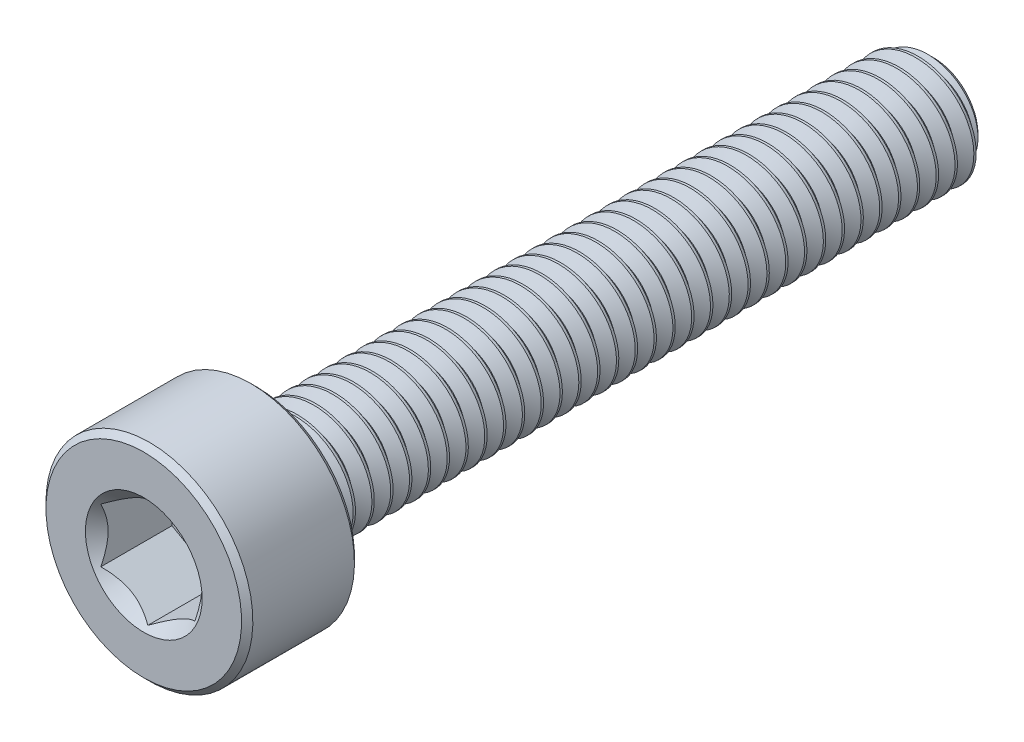
SolidWorks part; units mm, degrees
ref_plane "Front Plane" through (0, 0, 0) normal (0, 0, 1) x (1, 0, 0)
ref_plane "Top Plane" through (0, 0, 0) normal (0, 1, 0) x (1, 0, 0)
ref_plane "Right Plane" through (0, 0, 0) normal (1, 0, 0) x (0, 0, -1)
sketch "Sketch1" plane through (0, 0, 0) normal (1, 0, 0) x (0, 0, -1)
  line L0 (-10.5, 0) -> (10.5, 0) construction
  line L1 (10.5, 0) -> (10.5, 1.1752) construction
  line L2 (10.5, 1.1752) -> (10.1752, 1.5) construction
  line L3 (10.1752, 1.5) -> (10.125, 1.5) construction
  line L4 (10.125, 1.5) -> (-7.5, 1.5) construction
  line L5 (-7.5, 1.5) -> (-7.5, 2.75) construction
  line L6 (-7.5, 2.75) -> (-10.5, 2.75) construction
  line L7 (-10.5, 2.75) -> (-10.5, 0) construction
  line L8 (10.5, 1.1752) -> (10.5, 1.5) construction
  line L9 (10.4688, 1.5541) -> (10.7188, 1.1211) construction
  line L10 (10.7188, 1.1211) -> (10.9688, 1.5541) construction
  line L11 (10.9688, 1.5541) -> (10.4688, 1.5541) construction
  line L12 (10.7188, 1.5541) -> (10.7188, 1.5) construction
  line L13 (10.7188, 1.1211) -> (10.7188, 1.1752) construction
  line L14 (10.6875, 1.1752) -> (10.75, 1.1752) construction
  line L15 (10.5, 1.5) -> (10.9375, 1.5) construction
  line L16 (10.4844, 1.5271) -> (10.9531, 1.5271) construction
  line L17 (10.5, 0) -> (10.5, -1.5) construction
  line L18 (-7.65, 2.75) -> (-7.5, 2.6) construction
  line L19 (-10.35, 2.75) -> (-10.5, 2.6) construction
  line L20 (-7.5, 1.5) -> (-7.5, 0) construction
  line L21 (-7.5, 0.75) -> (-1.5, 0.75) construction
  line L22 (-1.5, 0.75) -> (4.5, 0.75) construction
  line L23 (4.5, 0.75) -> (10.5, 0.75) construction
  line L24 (-1.5, 0.75) -> (-1.5, 1.5) construction
  line L25 (-1.5, 1.5) -> (-1.5, 2.75) construction
  line L26 (4.5, 0.75) -> (4.5, 2.75) construction
  point P0 (-10.5, 1.25)
  point P3 (9.25, 1.5)
  point P4 (0, 0)
  point P18 (4.5, 1.5)
  point P22 (10.7188, 1.1752)
  point P24 (10.125, 1.5)
  point P25 (10.7188, 1.5)
  point P28 (10.7188, 1.5271)
  point P29 (9.25, -1.5)
  point P30 (-1.5, 1.5)
  point P31 (-9, 2.75)
  point P37 (-8.025, 2.75)
  point P38 (-10.275, 2.75)
  point P45 (-1.5, 0.75)
  point P46 (4.5, 0.75)
  dimension "D2" = 0.0625
  dimension "D7" = 0.15
  dimension "D8" = 0.15
  dimension "D9" = 0.15
  dimension "D10" = 0.075
  dimension "D11" = 0.375
  dimension "Drive Size" = 2.5
  dimension "Head Diameter" = 5.5
  dimension "Head Height" = 3
  dimension "Thread Pitch" = 0.5
  dimension "Thread Dia" = 3
  dimension "Length" = 18
  dimension "D12" = 0.375
  dimension "D4" = 1.25
  dimension "D3" = 45
sketch "Sketch2" plane through (0, 0, 0) normal (1, 0, 0) x (0, 0, -1)
  line L0 (-10.5, 0) -> (-10.5, 2.6)
  line L1 (-10.35, 2.75) -> (-7.65, 2.75)
  line L2 (-7.5, 2.6) -> (-7.5, 1.65)
  line L4 (10.1752, 1.5) -> (10.5, 1.1752)
  line L5 (10.5, 1.1752) -> (10.5, 0)
  line L6 (-7.5, 2.75) -> (-10.5, 2.75) construction
  line L7 (10.5, 0) -> (-10.5, 0)
  line L8 (-10.35, 2.75) -> (-10.5, 2.6) construction
  line L10 (-10.35, 2.75) -> (-10.5, 2.6)
  line L14 (-7.65, 2.75) -> (-7.5, 2.6) construction
  line L16 (-7.65, 2.75) -> (-7.5, 2.6)
  line L17 (-7.5, 1.5) -> (-7.5, 2.75) construction
  line L19 (-7.35, 1.5) -> (10.1752, 1.5)
  line L20 (10.125, 1.5) -> (-7.5, 1.5) construction
  arc A1 (-7.5, 1.65) -> (-7.35, 1.5) centre (-7.35, 1.65) ccw
  dimension "D3" = 0.15
revolve "Revolve1" add sketch "Sketch2" angle 360 about L7
sketch "Sketch3" plane through (0, 0, 10.5) normal (0, 0, 1) x (1, 0, 0)
  line L1 (1.25, -0.7217) -> (1.25, 0.7217)
  line L2 (1.25, 0.7217) -> (0, 1.4434)
  line L3 (0, 1.4434) -> (-1.25, 0.7217)
  line L4 (-1.25, 0.7217) -> (-1.25, -0.7217)
  line L5 (-1.25, -0.7217) -> (0, -1.4434)
  line L6 (0, -1.4434) -> (1.25, -0.7217)
  circle A0 centre (0, 0) radius 1.25 construction
  circle A1 centre (0, 0) radius 2.75 construction
  circle A2 centre (0, 0) radius 2.75 construction
  circle A3 centre (0, 0) radius 1.4434 construction
  point P13 (0, 0)
  dimension "D1" = 2.8868
extrude "Cut-Extrude1" cut sketch "Sketch3" against normal offset from surface (2 mm away) 1 up to face at (0, 2.6, 7.5)
sketch "Sketch4" plane through (0, 0, 10.5) normal (0, 0, 1) x (1, 0, 0)
  circle A0 centre (0, 0) radius 1.5516
  dimension "D1" = 3.1033
extrude "Cut-Extrude2" cut sketch "Sketch4" against normal up to vertex (1.5 mm away) draft 45 up to point (0, 2.75, 9)
sketch "Sketch11" plane through (0, 0, 0) normal (1, 0, 0) x (0, 0, -1)
  line L0 (-10.5, 0) -> (10.5, 0) construction
  line L1 (-10.5, 0) -> (10.5, 0) construction
  line L2 (-4.125, 0) -> (-4.125, 1.5) construction
  line L3 (10.125, 1.5) -> (-7.5, 1.5) construction
  line L4 (7.125, 0) -> (7.125, 1.5) construction
  line L6 (10.5, 1.1752) -> (10.5, 1.5) construction
  point P2 (-4.125, 0)
  point P3 (7.125, 0)
  dimension "D1" = 3.375
  dimension "D2" = 3.375
sketch "Sketch6" plane through (0, 0, -10.5) normal (0, 0, -1) x (-1, 0, 0)
  circle A0 centre (0, 0) radius 1.5
curve "Helix/Spiral1" pitch 0.5 height 18.5 turns 37
sketch "Sketch10" plane through (0, 0, 0) normal (1, 0, 0) x (0, 0, -1)
  line L0 (-7.35, -2.75) -> (-7.35, 2.75)
  line L5 (-10.5, 0) -> (10.5, 0) construction
  line L6 (-7.35, 1.5) -> (-7.35, -1.5) construction
  point P3 (-7.35, 0)
split "Split1" trim tools "Sketch10" bodies to split 106 resulting bodies 114 115
sketch "Sketch7" plane through (0, 0, 0) normal (1, 0, 0) x (0, 0, -1)
  line L0 (10.4844, 1.5271) -> (10.9531, 1.5271)
  line L1 (10.9531, 1.5271) -> (10.75, 1.1752)
  line L2 (10.75, 1.1752) -> (10.6875, 1.1752)
  line L3 (10.6875, 1.1752) -> (10.4844, 1.5271)
sweep "Cut-Sweep1" cut profiles "Sketch7" path "Helix/Spiral1"
sketch "Sketch8" plane through (0, 0, 0) normal (1, 0, 0) x (0, 0, -1)
  line L0 (-7.5, 0) -> (-7.5, 1.5)
  line L1 (-7.35, -1.5) -> (-7.35, 1.5) construction
  line L2 (-7.5, 1.5) -> (-7.35, 1.5)
  line L4 (-7.35, 1.5) -> (-6.484, 0)
  line L5 (-6.484, 0) -> (-7.5, 0)
  line L6 (10.125, 1.5) -> (-7.5, 1.5) construction
  line L7 (-10.5, 0) -> (10.5, 0) construction
  dimension "D1" = 60
revolve "Revolve2" add sketch "Sketch8" angle 360 about L5
equation "\"D2@Sketch1\" = \"Thread Pitch@Sketch1\" / 8"
equation "\"D4@Helix/Spiral1\" = \"Thread Pitch@Sketch1\""
equation "\"D7@Sketch1\" = \"Head Height@Sketch1\" * .05"
equation "\"D8@Sketch1\"=\"D7@Sketch1\""
equation "\"D9@Sketch1\"=\"D7@Sketch1\""
equation "\"D10@Sketch1\"=\"D7@Sketch1\"/2"
equation "\"D11@Sketch1\"=\"D10@Sketch1\"*5"
equation "\"D4@Sketch1\"=\"Thread Pitch@Sketch1\"*2.5"
equation "\"D12@Sketch1\"=\"Thread Pitch@Sketch1\"*.75"
equation "\"D3@Helix/Spiral1\"=\"Length@Sketch1\"+\"Thread Pitch@Sketch1\""
equation "\"D3@Sketch2\"=\"Thread Dia@Sketch1\"*0.05"
equation "\"D1@Sketch11\"=\"Length@Sketch1\"*0.1875"
equation "\"D2@Sketch11\"=\"D1@Sketch11\""
equation "\"D1@Sketch4\"=\"D1@Sketch3\"*1.075"
